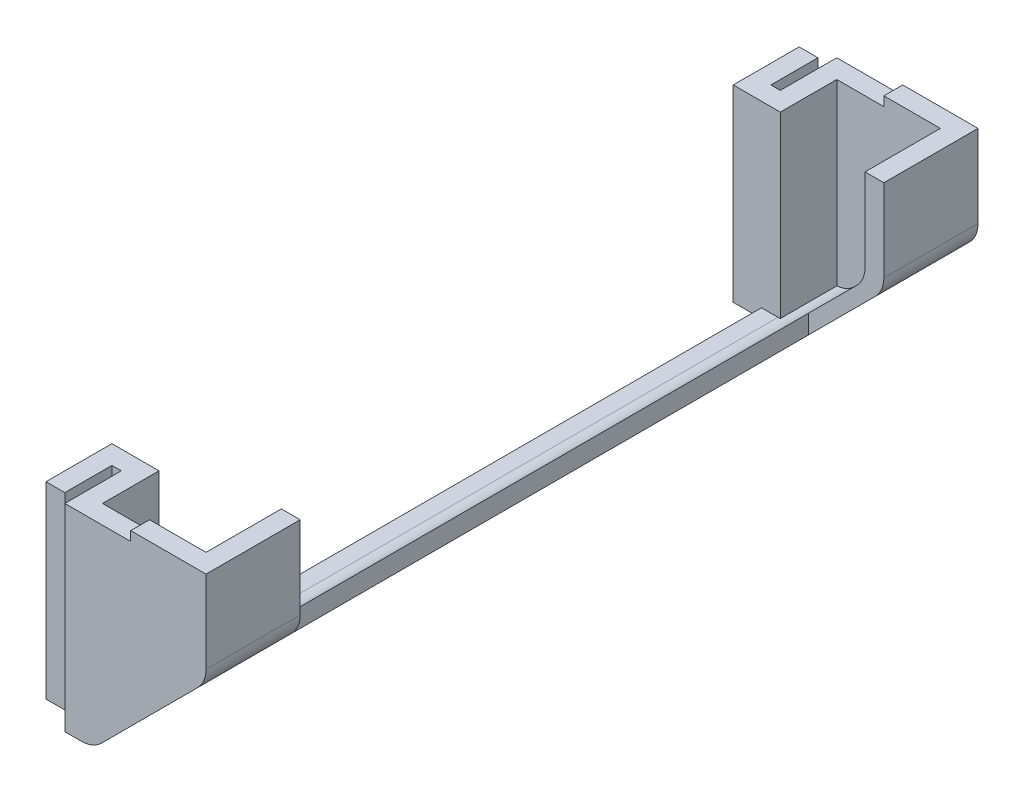
SolidWorks part; units mm, degrees
ref_plane "前视基准面" through (0, 0, 0) normal (0, 0, 1) x (1, 0, 0)
ref_plane "上视基准面" through (0, 0, 0) normal (0, 1, 0) x (1, 0, 0)
ref_plane "右视基准面" through (0, 0, 0) normal (1, 0, 0) x (0, 0, -1)
sketch "草图1" plane through (0, 0, 0) normal (0, 0, 1) x (1, 0, 0)
  line L0 (0, 0) -> (0, 2)
  line L1 (0, 2) -> (3, 2)
  line L5 (-60, 49) -> (3, 49)
  line L7 (0, 0) -> (3, 0)
  line L13 (3, 47) -> (-60, 47)
  line L15 (3, 2) -> (13, 12)
  line L16 (3, 0) -> (15, 12)
  line L17 (13, 37) -> (13, 12)
  line L18 (15, 12) -> (15, 37)
  line L19 (3, 47) -> (13, 37)
  line L20 (3, 49) -> (15, 37)
  line L21 (-60, 49) -> (-60, 47)
extrude "凸台-拉伸1" add sketch "草图1" along normal blind 82
fillet "圆角1" radius 3 8 edges at (3, 0, 41) (15, 12, 41) (15, 37, 41) (3, 49, 41) (3, 2, 41) (13, 12, 41) (13, 37, 41) (3, 47, 41)
sketch "草图4" plane through (0, 0, 0) normal (0, 0, -1) x (-1, 0, 0)
  line L0 (0, 0) -> (0, 26)
  line L1 (0, 26) -> (4, 26)
  line L2 (4, 26) -> (4, 27)
  line L3 (4, 27) -> (60, 27)
  line L4 (60, 27) -> (60, 49)
  line L5 (60, 49) -> (-1.7574, 49)
  line L6 (-1.7574, 49) -> (60, 49) construction
  line L7 (-3.8787, 48.1213) -> (-14.1213, 37.8787)
  line L8 (-15, 35.7574) -> (-15, 13.2426)
  line L9 (-14.1213, 11.1213) -> (-3.8787, 0.8787)
  line L10 (-1.7574, 0) -> (0, 0)
  arc A0 (-1.7574, 49) -> (-3.8787, 48.1213) centre (-1.7574, 46) ccw construction
  arc A1 (-1.7574, 49) -> (-3.8787, 48.1213) centre (-1.7574, 46) ccw
  arc A2 (-14.1213, 37.8787) -> (-15, 35.7574) centre (-12, 35.7574) ccw
  arc A3 (-15, 13.2426) -> (-14.1213, 11.1213) centre (-12, 13.2426) ccw
  arc A4 (-3.8787, 0.8787) -> (-1.7574, 0) centre (-1.7574, 3) ccw
extrude "凸台-拉伸2" add sketch "草图4" against normal blind 2
extrude "凸台-拉伸3" add sketch "草图4<2>" along normal blind 2 from offset 82 offset against normal yes
sketch "草图4<2>" plane through (0, 0, 0) normal (0, 0, -1) x (-1, 0, 0) same geometry as "草图4"
sketch "草图5" plane through (0, 0, 0) normal (0, 0, -1) x (-1, 0, 0)
  line L0 (2.6616, 45.0208) -> (2.6616, 31)
  line L1 (2.6616, 31) -> (0, 31)
  line L2 (0, 31) -> (0, 29.8631)
  line L3 (0, 29.8631) -> (56, 29.8631)
  line L4 (56, 29.8631) -> (56, 31)
  line L5 (56, 31) -> (53.4695, 31)
  line L6 (53.4695, 31) -> (53.4695, 44.3)
  line L7 (53.4695, 44.3) -> (37.4695, 44.3)
  line L8 (37.4695, 44.3) -> (37.4695, 31)
  line L9 (37.4695, 31) -> (36.113, 31)
  line L10 (36.113, 31) -> (36.113, 38.112)
  line L11 (36.113, 38.112) -> (19.513, 38.112)
  line L12 (19.513, 38.112) -> (19.513, 31)
  line L13 (19.513, 31) -> (17.8616, 31)
  line L14 (17.8616, 31) -> (17.8616, 45.0208)
  line L15 (17.8616, 45.0208) -> (2.6616, 45.0208)
extrude "切除-拉伸1" cut sketch "草图5" against normal blind 2
sketch "草图6" plane through (0, 0, 82) normal (0, 0, 1) x (1, 0, 0)
  line L13 (-56, 31) -> (-49.5434, 31)
  line L14 (-49.5434, 31) -> (-49.5434, 37.1214)
  line L15 (-49.5434, 37.1214) -> (-33.1434, 37.1214)
  line L16 (-33.1434, 37.1214) -> (-33.1434, 32.1214)
  line L17 (-33.1434, 37.1214) -> (-33.1434, 31) construction
  line L18 (-33.1434, 32.1214) -> (-29.1434, 32.1214)
  line L19 (-29.1434, 32.1214) -> (-29.1434, 31)
  line L20 (-3, 31) -> (-33.1434, 31) construction
  line L21 (-29.1434, 31) -> (-10.3442, 31)
  line L22 (-10.3442, 31) -> (-10.3442, 33.5)
  line L23 (-10.3442, 33.5) -> (-6.3442, 33.5)
  line L24 (-6.3442, 33.5) -> (-6.3442, 31)
  line L25 (-6.3442, 31) -> (0, 31)
  line L26 (-56, 31) -> (-56, 27)
  line L27 (-4, 27) -> (-60, 27) construction
  line L29 (0, 27) -> (0, 31)
  line L30 (0, 27) -> (0, 26)
  line L31 (0, 26) -> (-4, 26)
  line L32 (-4, 26) -> (-4, 27)
  line L33 (-4, 27) -> (-56, 27)
extrude "切除-拉伸2" cut sketch "草图6" against normal blind 2
sketch "草图7" plane through (0, 49, 0) normal (0, 1, 0) x (1, 0, 0)
  line L0 (-50, -66) -> (-50, -78)
  line L6 (-50, -66) -> (-50, -41)
  line L9 (-60, -82) -> (-60, 0) construction
  line L16 (-57, -26.4948) -> (-52.4369, -26.4948)
  line L17 (-60, -23.4948) -> (-60, -80)
  line L18 (-50, -41) -> (-50, -28.9317)
  line L21 (-38.7426, -20.5) -> (-38.7426, -16)
  line L24 (-43.7426, -25.5) -> (-48.2426, -25.5)
  line L26 (-60, -80) -> (-56, -80)
  line L27 (-7.7426, -16) -> (-38.7426, -16)
  line L28 (1.7574, -80) -> (-60, -80) construction
  line L29 (-54, -78) -> (-50, -78)
  line L30 (-48.2426, -56.5) -> (-48.2426, -25.5)
  line L31 (-2.7426, -56.5) -> (1.7574, -56.5)
  line L33 (-7.7426, -20.5) -> (-7.7426, -16)
  line L34 (-2.7426, -25.5) -> (1.7574, -25.5)
  line L35 (1.7574, -56.5) -> (1.7574, -25.5)
  line L36 (-7.7426, -61.5) -> (-7.7426, -66)
  line L37 (-7.7426, -66) -> (-38.7426, -66)
  line L38 (-43.7426, -56.5) -> (-48.2426, -56.5)
  line L39 (-38.7426, -61.5) -> (-38.7426, -66)
  circle A2 centre (-52.4948, -81.4948) radius 2
  circle A5 centre (-3.4982, -81.4948) radius 2
  arc A7 (-52.4369, -26.4948) -> (-50, -28.9317) centre (-52.4369, -28.9317) cw
  arc A8 (-60, -23.4948) -> (-57, -26.4948) centre (-57, -23.4948) ccw
  arc A10 (-56, -80) -> (-54, -78) centre (-54, -80) cw
  circle A11 centre (-43.7426, -20.5) radius 3.3
  arc A15 (-43.7426, -25.5) -> (-38.7426, -20.5) centre (-43.7426, -20.5) ccw
  circle A16 centre (-2.7426, -20.5) radius 3.3
  arc A17 (-2.7426, -25.5) -> (-7.7426, -20.5) centre (-2.7426, -20.5) cw
  arc A18 (-2.7426, -56.5) -> (-7.7426, -61.5) centre (-2.7426, -61.5) ccw
  circle A19 centre (-2.7426, -61.5) radius 3.3
  arc A20 (-43.7426, -56.5) -> (-38.7426, -61.5) centre (-43.7426, -61.5) cw
  circle A21 centre (-43.7426, -61.5) radius 3.3
extrude "切除-拉伸3" cut sketch "草图7" against normal up to next
sketch "草图8" plane through (0, 49, 0) normal (0, 1, 0) x (1, 0, 0)
  line L1 (-6.3442, -79) -> (0, -79)
  line L2 (0, -79) -> (0, -82)
  line L6 (-6.3442, -82) -> (-6.3442, -85)
  line L7 (-3, -85) -> (-33.1434, -85) construction
  line L8 (-6.3442, -85) -> (-3, -85)
  line L9 (-49.5434, -82) -> (-49.5434, -79)
  line L10 (-49.5434, -86.4622) -> (-49.5434, -73.9622) construction
  line L13 (-56, -79) -> (-49.5434, -79)
  line L15 (-53, -85) -> (-49.5434, -85)
  line L16 (-49.5434, -85) -> (-49.5434, -82)
  line L17 (-54.4299, -82) -> (-60, -82) construction
  line L18 (-56, -79) -> (-56, -82)
  line L19 (-6.3442, -79) -> (-6.3442, -82)
  circle A0 centre (-52.4948, -81.4948) radius 2
  circle A2 centre (-3.4982, -81.4948) radius 2
  arc A3 (0, -82) -> (-3, -85) centre (-3, -82) cw
  arc A5 (-53, -85) -> (-56, -82) centre (-53, -82) cw
extrude "凸台-拉伸4" add sketch "草图8" against normal blind 18
sketch "草图9" plane through (0, 0, 0) normal (-1, 0, 0) x (0, 0, 1)
  line L2 (1, 1) -> (8, 1)
  line L3 (8, 1) -> (8, 21)
  line L4 (8, 21) -> (1, 21)
  line L5 (1, 21) -> (1, 1)
  line L6 (81, 21) -> (81, 1)
  line L7 (74, 21) -> (81, 21)
  line L8 (74, 1) -> (74, 21)
  line L9 (81, 1) -> (74, 1)
extrude "凸台-拉伸5" add sketch "草图9" against normal blind 2
sketch "草图10" plane through (0, 0, 0) normal (-1, 0, 0) x (0, 0, 1)
  line L0 (8, 21) -> (6, 21)
  line L1 (8, 21) -> (2, 21) construction
  line L2 (6, 21) -> (6, 1)
  line L3 (6, 1) -> (8, 1)
  line L4 (8, 1) -> (8, 21)
  line L7 (74, 1) -> (74, 21)
  line L8 (76, 1) -> (74, 1)
  line L9 (76, 21) -> (76, 1)
  line L10 (74, 21) -> (76, 21)
extrude "凸台-拉伸6" add sketch "草图10" along normal blind 1
sketch "草图11" plane through (-1, 0, 0) normal (-1, 0, 0) x (0, 0, 1)
  line L0 (8, 21) -> (1, 21)
  line L1 (1, 21) -> (1, 1)
  line L2 (1, 1) -> (8, 1)
  line L3 (8, 1) -> (8, 21)
  line L6 (74, 1) -> (74, 21)
  line L7 (81, 1) -> (74, 1)
  line L8 (81, 21) -> (81, 1)
  line L9 (74, 21) -> (81, 21)
extrude "凸台-拉伸7" add sketch "草图11" along normal blind 2
sketch "草图12" plane through (15, 0, 0) normal (1, 0, 0) x (0, 0, -1)
  line L0 (-82, 0) -> (-72, 0)
  line L1 (0, 0) -> (-82, 0) construction
  line L2 (-72, 0) -> (-72, 22)
  line L3 (-72, 22) -> (-82, 22)
  line L4 (-82, 13.2426) -> (-82, 35.7574) construction
  line L5 (-82, 22) -> (-82, 0)
  line L7 (0, 22) -> (0, 0)
  line L8 (-10, 22) -> (0, 22)
  line L9 (-10, 0) -> (-10, 22)
  line L10 (0, 0) -> (-10, 0)
extrude "切除-拉伸4" cut sketch "草图12" against normal blind 8 flip side to cut
sketch "草图13" plane through (0, 0, 0) normal (0, -1, 0) x (1, 0, 0)
  line L0 (0, 0) -> (-4, 0) construction
  line L1 (7, 82) -> (-3, 82)
  line L2 (7, 82) -> (7, 0)
  line L3 (7, 0) -> (-3, 0)
  line L4 (-3, 82) -> (-3, 0)
sketch "草图14" plane through (0, 21, 0) normal (0, 1, 0) x (1, 0, 0)
  line L1 (7, 0) -> (-86.1299, 0)
  line L2 (7, 0) -> (7, -88.4499)
  line L3 (7, -88.4499) -> (-86.1299, -88.4499)
  line L4 (-86.1299, 0) -> (-86.1299, -88.4499)
extrude "切除-拉伸5" cut sketch "草图14" along normal through all
